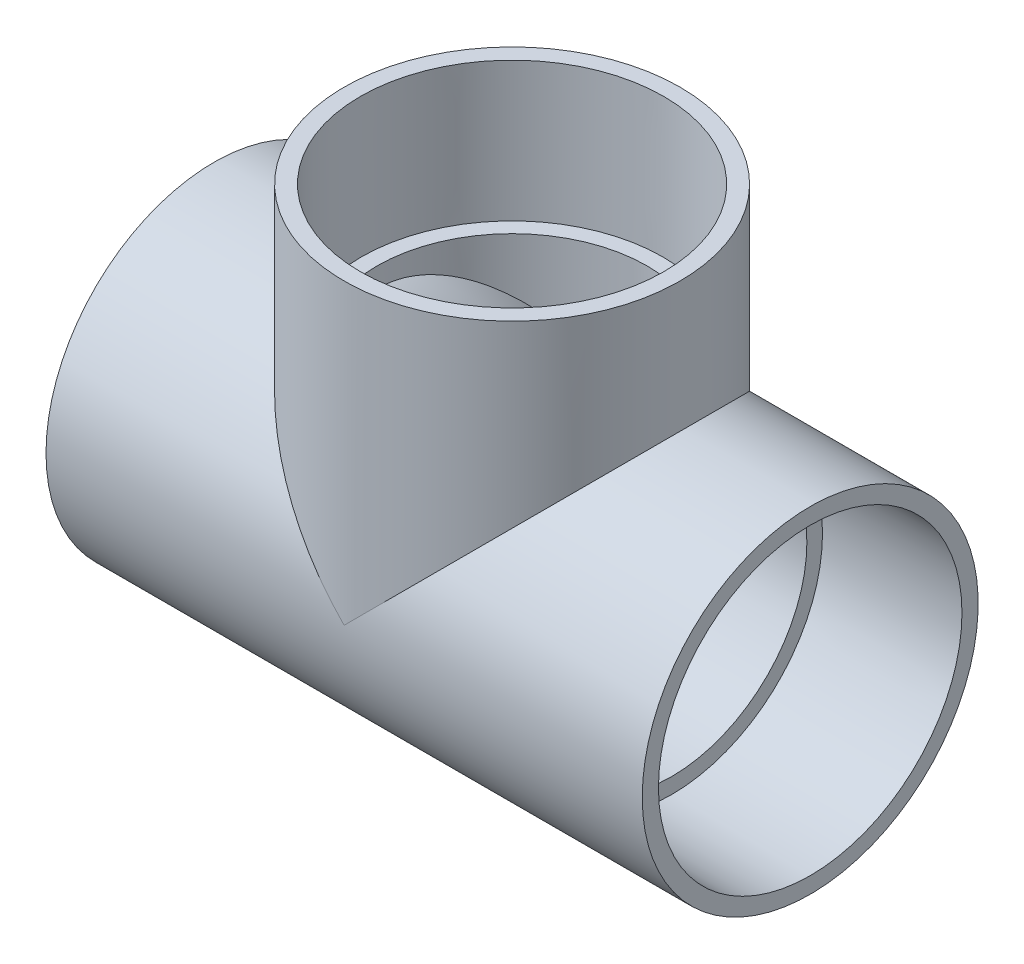
SolidWorks part; units mm, degrees
ref_plane "Front Plane" through (0, 0, 0) normal (0, 0, 1) x (1, 0, 0)
ref_plane "Top Plane" through (0, 0, 0) normal (0, 1, 0) x (1, 0, 0)
ref_plane "Right Plane" through (0, 0, 0) normal (1, 0, 0) x (0, 0, -1)
sketch "Sketch0" plane through (0, 0, 0) normal (0, 0, 1) x (1, 0, 0)
  line L0 (-112.7125, 0) -> (0, 0) construction
  line L1 (0, 0) -> (0, 112.7125) construction
  line L2 (-60.325, 0) -> (0, 0) construction
  line L3 (0, 0) -> (0, 60.325) construction
  line L4 (-112.7125, 63.5) -> (-112.7125, -63.5) construction
  line L5 (-60.325, 57.0357) -> (-112.7125, 57.3786) construction
  line L6 (-60.325, 57.0357) -> (-60.325, -57.0357) construction
  line L7 (-60.325, -57.0357) -> (-112.7125, -57.3786) construction
  line L8 (-112.7125, 57.3786) -> (-112.7125, -57.3786) construction
  line L9 (-63.5, 112.7125) -> (63.5, 112.7125) construction
  line L10 (-57.3786, 112.7125) -> (57.3786, 112.7125) construction
  line L11 (57.3786, 112.7125) -> (57.0357, 60.325) construction
  line L12 (57.0357, 60.325) -> (-57.0357, 60.325) construction
  line L13 (-57.0357, 60.325) -> (-57.3786, 112.7125) construction
  line L14 (-60.325, 51.1302) -> (-60.325, -51.1302) construction
  line L18 (-51.1302, 60.325) -> (51.1302, 60.325) construction
  dimension "H" = 112.7125
  dimension "G" = 60.325
  dimension "M" = 127
  dimension "OD A" = 114.7572
  dimension "OD B" = 114.0714
  dimension "ID" = 102.2604
sketch "Sketch1" plane through (0, 0, 0) normal (0, 0, 1) x (1, 0, 0)
  line L0 (-112.7125, 0) -> (0, 0) construction
  line L1 (-112.7125, 0) -> (0, 0) construction
  line L3 (-112.7125, -63.5) -> (-60.325, -63.5)
  line L4 (-112.7125, -63.5) -> (-112.7125, -57.3786)
  line L5 (-112.7125, -57.3786) -> (-60.325, -57.0357)
  line L6 (-60.325, -63.5) -> (-60.325, -57.0357)
revolve "Revolve1" add sketch "Sketch1" angle 360 about L1
mirror "Mirror1" about plane through (0, 0, 0) normal (1, 0, 0) of bodies 102
sketch "Sketch2" plane through (0, 0, 0) normal (0, 0, 1) x (1, 0, 0)
  line L0 (57.3786, 112.7125) -> (57.0357, 60.325)
  line L1 (57.0357, 60.325) -> (63.5, 60.325)
  line L2 (63.5, 60.325) -> (63.5, 112.7125)
  line L3 (63.5, 112.7125) -> (57.3786, 112.7125)
  line L4 (0, 0) -> (0, 112.7125) construction
  line L5 (0, 0) -> (0, 112.7125) construction
revolve "Revolve2" add sketch "Sketch2" angle 360 about L5
sketch "Sketch3" plane through (-60.325, 0, 0) normal (1, 0, 0) x (0, 0, -1)
  line L0 (-63.5, 60.325) -> (63.5, 60.325) construction
  line L2 (19.8279, 60.325) -> (-19.8279, 60.325)
  circle A1 centre (0, 0) radius 63.5 construction
  arc A3 (-19.8279, 60.325) -> (19.8279, 60.325) centre (0, 0) ccw
extrude "Boss-Extrude1" add sketch "Sketch3" along normal up to surface (120.65 mm away) up to face at (60.325, 0, 57.0357)
sketch "Sketch4" plane through (0, 60.325, 0) normal (0, -1, 0) x (1, 0, 0)
  line L0 (60.325, -19.8279) -> (60.325, 19.8279)
  line L1 (-60.325, -19.8279) -> (-60.325, 19.8279)
  circle A0 centre (0, 0) radius 63.5 construction
  arc A1 (60.325, 19.8279) -> (-60.325, 19.8279) centre (0, 0) ccw
  arc A2 (-60.325, -19.8279) -> (60.325, -19.8279) centre (0, 0) ccw
  circle A3 centre (0, 0) radius 63.5 construction
  circle A4 centre (0, 0) radius 63.5 construction
extrude "Boss-Extrude2" add sketch "Sketch4" along normal up to surface (60.325 mm away) up to plane "Top Plane"
sketch "Sketch5" plane through (-60.325, 0, 0) normal (-1, 0, 0) x (0, 0, 1)
  line L0 (0, 57.0357) -> (0, -57.0357) construction
  circle A0 centre (0, 0) radius 51.1302
extrude "Cut-Extrude1" cut sketch "Sketch5" against normal up to surface (120.65 mm away) up to face at (60.325, 0, 57.0357)
sketch "Sketch6" plane through (0, 60.325, 0) normal (0, 1, 0) x (1, 0, 0)
  circle A0 centre (0, 0) radius 51.1302
extrude "Cut-Extrude2" cut sketch "Sketch6" against normal up to vertex (60.325 mm away) up to point (0, 0, 0)
other "CPoint1" parameters "Diameter"=101.6, "StubLength"=228.6
ref_axis "Axis1" through (-70.325, 0, 0) along (1, 0, 0)
other "CPoint2" parameters "Diameter"=101.6, "StubLength"=228.6
ref_axis "Axis2" through (70.325, 0, 0) along (-1, 0, 0)
other "CPoint3" parameters "Diameter"=101.6, "StubLength"=152.4
ref_axis "Axis3" through (0, 70.325, 0) along (0, -1, 0)
other "RPoint1"
